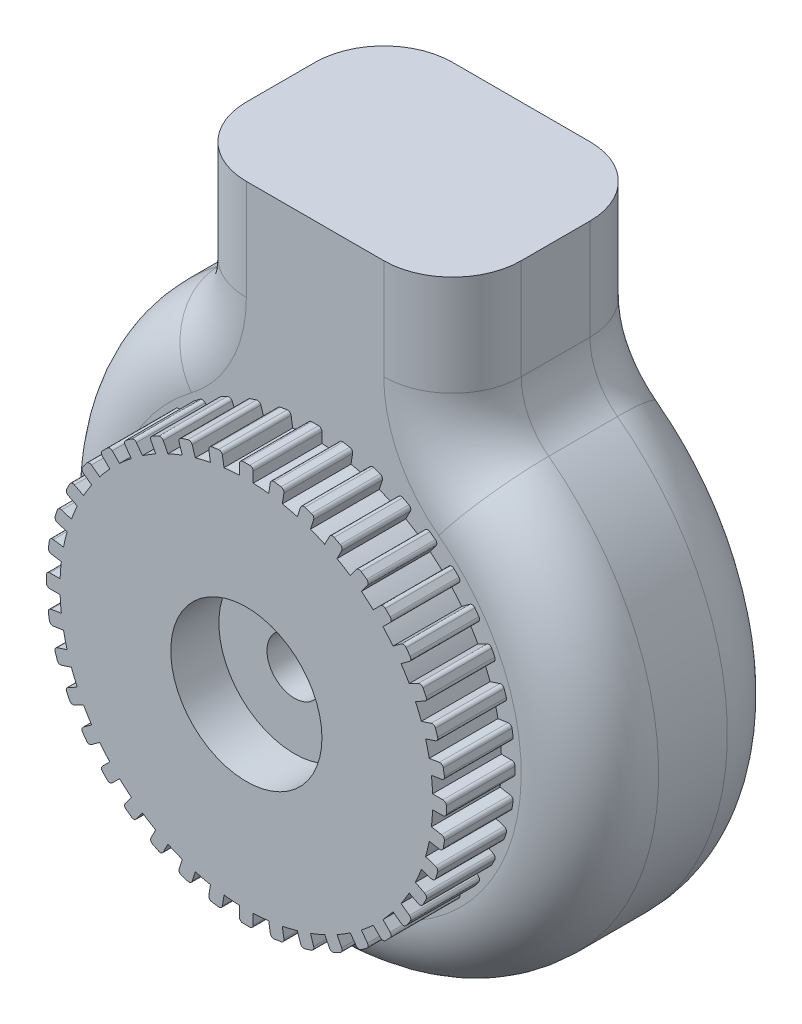
SolidWorks part; units mm, degrees
material "ABS"
ref_plane "Plan de face" through (0, 0, 0) normal (0, 0, 1) x (1, 0, 0)
ref_plane "Plan de dessus" through (0, 0, 0) normal (0, 1, 0) x (1, 0, 0)
ref_plane "Plan de droite" through (0, 0, 0) normal (1, 0, 0) x (0, 0, -1)
sketch "Esquisse1" plane through (0, 0, 0) normal (0, 0, 1) x (1, 0, 0)
  line L0 (0, -1000) -> (0, 49000) construction
  line L1 (-20, 34.641) -> (-20, 54.641)
  line L2 (-20, 54.641) -> (20, 54.641)
  line L3 (20, 34.641) -> (20, 54.641)
  circle A0 centre (0, 0) radius 40
  point P3 (-20, 34.641)
  point P11 (0, 54.641)
  dimension "D1" = 80
  dimension "D2" = 20
  dimension "D3" = 20
extrude "Boss.-Extru.1" add sketch "Esquisse1" along normal blind 15 and the other way blind 15 contours A0 L0 | A0 L0 L2 L1 | L0 A0 L3 L2 | L0 A0 region at (-16.9765, 0, 0) region at (16.9765, 0, 0) region at (-10.5372, 46.3765, 0) region at (10.5372, 46.3765, 0)
sketch "Esquisse3" plane through (0, 0, -15) normal (0, 0, -1) x (-1, 0, 0)
  circle A0 centre (0, 0) radius 15
  dimension "D1" = 30
extrude "Boss.-Extru.2" add sketch "Esquisse3" along normal blind 10
sketch "Esquisse4" plane through (0, 0, 15) normal (0, 0, 1) x (1, 0, 0)
  line L0 (0, -1000) -> (0, 49000) construction
  line L1 (-1, 27.1005) -> (-1, 28.6005)
  line L2 (-0.5, 29.1005) -> (0.5, 29.1005)
  line L3 (1, 27.1005) -> (1, 28.6005)
  line L4 (5.2271, 26.6104) -> (5.4618, 28.0919)
  line L5 (3.2518, 26.9232) -> (3.4864, 28.4048)
  line L6 (4.0585, 28.8204) -> (5.0462, 28.664)
  line L7 (9.3256, 25.465) -> (9.7891, 26.8916)
  line L8 (7.4234, 26.0831) -> (7.887, 27.5097)
  line L9 (8.517, 27.8307) -> (9.4681, 27.5217)
  line L10 (13.1944, 23.6927) -> (13.8753, 25.0292)
  line L11 (11.4123, 24.6007) -> (12.0933, 25.9372)
  line L12 (12.7658, 26.1557) -> (13.6568, 25.7017)
  line L13 (16.7383, 21.3369) -> (17.6199, 22.5505)
  line L14 (15.1202, 22.5125) -> (16.0019, 23.726)
  line L15 (16.7003, 23.8367) -> (17.5093, 23.2489)
  line L16 (19.87, 18.4558) -> (20.9307, 19.5165)
  line L17 (18.4558, 19.87) -> (19.5165, 20.9307)
  line L18 (20.2236, 20.9307) -> (20.9307, 20.2236)
  line L19 (22.5125, 15.1202) -> (23.726, 16.0019)
  line L20 (21.3369, 16.7383) -> (22.5505, 17.6199)
  line L21 (23.2489, 17.5093) -> (23.8367, 16.7003)
  line L22 (24.6007, 11.4123) -> (25.9372, 12.0933)
  line L23 (23.6927, 13.1944) -> (25.0292, 13.8753)
  line L24 (25.7017, 13.6568) -> (26.1557, 12.7658)
  line L25 (26.0831, 7.4234) -> (27.5097, 7.887)
  line L26 (25.465, 9.3256) -> (26.8916, 9.7891)
  line L27 (27.5217, 9.4681) -> (27.8307, 8.517)
  line L28 (26.9232, 3.2518) -> (28.4048, 3.4864)
  line L29 (26.6104, 5.2271) -> (28.0919, 5.4618)
  line L30 (28.664, 5.0462) -> (28.8204, 4.0585)
  line L31 (27.1005, -1) -> (28.6005, -1)
  line L32 (27.1005, 1) -> (28.6005, 1)
  line L33 (29.1005, 0.5) -> (29.1005, -0.5)
  line L34 (26.6104, -5.2271) -> (28.0919, -5.4618)
  line L35 (26.9232, -3.2518) -> (28.4048, -3.4864)
  line L36 (28.8204, -4.0585) -> (28.664, -5.0462)
  line L37 (25.465, -9.3256) -> (26.8916, -9.7891)
  line L38 (26.0831, -7.4234) -> (27.5097, -7.887)
  line L39 (27.8307, -8.517) -> (27.5217, -9.4681)
  line L40 (23.6927, -13.1944) -> (25.0292, -13.8753)
  line L41 (24.6007, -11.4123) -> (25.9372, -12.0933)
  line L42 (26.1557, -12.7658) -> (25.7017, -13.6568)
  line L43 (21.3369, -16.7383) -> (22.5505, -17.6199)
  line L44 (22.5125, -15.1202) -> (23.726, -16.0019)
  line L45 (23.8367, -16.7003) -> (23.2489, -17.5093)
  line L46 (18.4558, -19.87) -> (19.5165, -20.9307)
  line L47 (19.87, -18.4558) -> (20.9307, -19.5165)
  line L48 (20.9307, -20.2236) -> (20.2236, -20.9307)
  line L49 (15.1202, -22.5125) -> (16.0019, -23.726)
  line L50 (16.7383, -21.3369) -> (17.6199, -22.5505)
  line L51 (17.5093, -23.2489) -> (16.7003, -23.8367)
  line L52 (11.4123, -24.6007) -> (12.0933, -25.9372)
  line L53 (13.1944, -23.6927) -> (13.8753, -25.0292)
  line L54 (13.6568, -25.7017) -> (12.7658, -26.1557)
  line L55 (7.4234, -26.0831) -> (7.887, -27.5097)
  line L56 (9.3256, -25.465) -> (9.7891, -26.8916)
  line L57 (9.4681, -27.5217) -> (8.517, -27.8307)
  line L58 (3.2518, -26.9232) -> (3.4864, -28.4048)
  line L59 (5.2271, -26.6104) -> (5.4618, -28.0919)
  line L60 (5.0462, -28.664) -> (4.0585, -28.8204)
  line L61 (-1, -27.1005) -> (-1, -28.6005)
  line L62 (1, -27.1005) -> (1, -28.6005)
  line L63 (0.5, -29.1005) -> (-0.5, -29.1005)
  line L64 (-5.2271, -26.6104) -> (-5.4618, -28.0919)
  line L65 (-3.2518, -26.9232) -> (-3.4864, -28.4048)
  line L66 (-4.0585, -28.8204) -> (-5.0462, -28.664)
  line L67 (-9.3256, -25.465) -> (-9.7891, -26.8916)
  line L68 (-7.4234, -26.0831) -> (-7.887, -27.5097)
  line L69 (-8.517, -27.8307) -> (-9.4681, -27.5217)
  line L70 (-13.1944, -23.6927) -> (-13.8753, -25.0292)
  line L71 (-11.4123, -24.6007) -> (-12.0933, -25.9372)
  line L72 (-12.7658, -26.1557) -> (-13.6568, -25.7017)
  line L73 (-16.7383, -21.3369) -> (-17.6199, -22.5505)
  line L74 (-15.1202, -22.5125) -> (-16.0019, -23.726)
  line L75 (-16.7003, -23.8367) -> (-17.5093, -23.2489)
  line L76 (-19.87, -18.4558) -> (-20.9307, -19.5165)
  line L77 (-18.4558, -19.87) -> (-19.5165, -20.9307)
  line L78 (-20.2236, -20.9307) -> (-20.9307, -20.2236)
  line L79 (-22.5125, -15.1202) -> (-23.726, -16.0019)
  line L80 (-21.3369, -16.7383) -> (-22.5505, -17.6199)
  line L81 (-23.2489, -17.5093) -> (-23.8367, -16.7003)
  line L82 (-24.6007, -11.4123) -> (-25.9372, -12.0933)
  line L83 (-23.6927, -13.1944) -> (-25.0292, -13.8753)
  line L84 (-25.7017, -13.6568) -> (-26.1557, -12.7658)
  line L85 (-26.0831, -7.4234) -> (-27.5097, -7.887)
  line L86 (-25.465, -9.3256) -> (-26.8916, -9.7891)
  line L87 (-27.5217, -9.4681) -> (-27.8307, -8.517)
  line L88 (-26.9232, -3.2518) -> (-28.4048, -3.4864)
  line L89 (-26.6104, -5.2271) -> (-28.0919, -5.4618)
  line L90 (-28.664, -5.0462) -> (-28.8204, -4.0585)
  line L91 (-27.1005, 1) -> (-28.6005, 1)
  line L92 (-27.1005, -1) -> (-28.6005, -1)
  line L93 (-29.1005, -0.5) -> (-29.1005, 0.5)
  line L94 (-26.6104, 5.2271) -> (-28.0919, 5.4618)
  line L95 (-26.9232, 3.2518) -> (-28.4048, 3.4864)
  line L96 (-28.8204, 4.0585) -> (-28.664, 5.0462)
  line L97 (-25.465, 9.3256) -> (-26.8916, 9.7891)
  line L98 (-26.0831, 7.4234) -> (-27.5097, 7.887)
  line L99 (-27.8307, 8.517) -> (-27.5217, 9.4681)
  line L100 (-23.6927, 13.1944) -> (-25.0292, 13.8753)
  line L101 (-24.6007, 11.4123) -> (-25.9372, 12.0933)
  line L102 (-26.1557, 12.7658) -> (-25.7017, 13.6568)
  line L103 (-21.3369, 16.7383) -> (-22.5505, 17.6199)
  line L104 (-22.5125, 15.1202) -> (-23.726, 16.0019)
  line L105 (-23.8367, 16.7003) -> (-23.2489, 17.5093)
  line L106 (-18.4558, 19.87) -> (-19.5165, 20.9307)
  line L107 (-19.87, 18.4558) -> (-20.9307, 19.5165)
  line L108 (-20.9307, 20.2236) -> (-20.2236, 20.9307)
  line L109 (-15.1202, 22.5125) -> (-16.0019, 23.726)
  line L110 (-16.7383, 21.3369) -> (-17.6199, 22.5505)
  line L111 (-17.5093, 23.2489) -> (-16.7003, 23.8367)
  line L112 (-11.4123, 24.6007) -> (-12.0933, 25.9372)
  line L113 (-13.1944, 23.6927) -> (-13.8753, 25.0292)
  line L114 (-13.6568, 25.7017) -> (-12.7658, 26.1557)
  line L115 (-7.4234, 26.0831) -> (-7.887, 27.5097)
  line L116 (-9.3256, 25.465) -> (-9.7891, 26.8916)
  line L117 (-9.4681, 27.5217) -> (-8.517, 27.8307)
  line L118 (-3.2518, 26.9232) -> (-3.4864, 28.4048)
  line L119 (-5.2271, 26.6104) -> (-5.4618, 28.0919)
  line L120 (-5.0462, 28.664) -> (-4.0585, 28.8204)
  arc A1 (-1, 28.6005) -> (-0.5, 29.1005) centre (-0.5, 28.6005) cw
  arc A2 (1, 28.6005) -> (0.5, 29.1005) centre (0.5, 28.6005) ccw
  arc A3 (5.4618, 28.0919) -> (5.0462, 28.664) centre (4.9679, 28.1701) ccw
  arc A4 (3.4864, 28.4048) -> (4.0585, 28.8204) centre (3.9803, 28.3266) cw
  arc A5 (9.7891, 26.8916) -> (9.4681, 27.5217) centre (9.3136, 27.0461) ccw
  arc A6 (7.887, 27.5097) -> (8.517, 27.8307) centre (8.3625, 27.3552) cw
  arc A7 (13.8753, 25.0292) -> (13.6568, 25.7017) centre (13.4298, 25.2562) ccw
  arc A8 (12.0933, 25.9372) -> (12.7658, 26.1557) centre (12.5388, 25.7102) cw
  arc A9 (17.6199, 22.5505) -> (17.5093, 23.2489) centre (17.2154, 22.8444) ccw
  arc A10 (16.0019, 23.726) -> (16.7003, 23.8367) centre (16.4064, 23.4321) cw
  arc A11 (20.9307, 19.5165) -> (20.9307, 20.2236) centre (20.5771, 19.87) ccw
  arc A12 (19.5165, 20.9307) -> (20.2236, 20.9307) centre (19.87, 20.5771) cw
  arc A13 (23.726, 16.0019) -> (23.8367, 16.7003) centre (23.4321, 16.4064) ccw
  arc A14 (22.5505, 17.6199) -> (23.2489, 17.5093) centre (22.8444, 17.2154) cw
  arc A15 (25.9372, 12.0933) -> (26.1557, 12.7658) centre (25.7102, 12.5388) ccw
  arc A16 (25.0292, 13.8753) -> (25.7017, 13.6568) centre (25.2562, 13.4298) cw
  arc A17 (27.5097, 7.887) -> (27.8307, 8.517) centre (27.3552, 8.3625) ccw
  arc A18 (26.8916, 9.7891) -> (27.5217, 9.4681) centre (27.0461, 9.3136) cw
  arc A19 (28.4048, 3.4864) -> (28.8204, 4.0585) centre (28.3266, 3.9803) ccw
  arc A20 (28.0919, 5.4618) -> (28.664, 5.0462) centre (28.1701, 4.9679) cw
  arc A21 (28.6005, -1) -> (29.1005, -0.5) centre (28.6005, -0.5) ccw
  arc A22 (28.6005, 1) -> (29.1005, 0.5) centre (28.6005, 0.5) cw
  arc A23 (28.0919, -5.4618) -> (28.664, -5.0462) centre (28.1701, -4.9679) ccw
  arc A24 (28.4048, -3.4864) -> (28.8204, -4.0585) centre (28.3266, -3.9803) cw
  arc A25 (26.8916, -9.7891) -> (27.5217, -9.4681) centre (27.0461, -9.3136) ccw
  arc A26 (27.5097, -7.887) -> (27.8307, -8.517) centre (27.3552, -8.3625) cw
  arc A27 (25.0292, -13.8753) -> (25.7017, -13.6568) centre (25.2562, -13.4298) ccw
  arc A28 (25.9372, -12.0933) -> (26.1557, -12.7658) centre (25.7102, -12.5388) cw
  arc A29 (22.5505, -17.6199) -> (23.2489, -17.5093) centre (22.8444, -17.2154) ccw
  arc A30 (23.726, -16.0019) -> (23.8367, -16.7003) centre (23.4321, -16.4064) cw
  arc A31 (19.5165, -20.9307) -> (20.2236, -20.9307) centre (19.87, -20.5771) ccw
  arc A32 (20.9307, -19.5165) -> (20.9307, -20.2236) centre (20.5771, -19.87) cw
  arc A33 (16.0019, -23.726) -> (16.7003, -23.8367) centre (16.4064, -23.4321) ccw
  arc A34 (17.6199, -22.5505) -> (17.5093, -23.2489) centre (17.2154, -22.8444) cw
  arc A35 (12.0933, -25.9372) -> (12.7658, -26.1557) centre (12.5388, -25.7102) ccw
  arc A36 (13.8753, -25.0292) -> (13.6568, -25.7017) centre (13.4298, -25.2562) cw
  arc A37 (7.887, -27.5097) -> (8.517, -27.8307) centre (8.3625, -27.3552) ccw
  arc A38 (9.7891, -26.8916) -> (9.4681, -27.5217) centre (9.3136, -27.0461) cw
  arc A39 (3.4864, -28.4048) -> (4.0585, -28.8204) centre (3.9803, -28.3266) ccw
  arc A40 (5.4618, -28.0919) -> (5.0462, -28.664) centre (4.9679, -28.1701) cw
  arc A41 (-1, -28.6005) -> (-0.5, -29.1005) centre (-0.5, -28.6005) ccw
  arc A42 (1, -28.6005) -> (0.5, -29.1005) centre (0.5, -28.6005) cw
  arc A43 (-5.4618, -28.0919) -> (-5.0462, -28.664) centre (-4.9679, -28.1701) ccw
  arc A44 (-3.4864, -28.4048) -> (-4.0585, -28.8204) centre (-3.9803, -28.3266) cw
  arc A45 (-9.7891, -26.8916) -> (-9.4681, -27.5217) centre (-9.3136, -27.0461) ccw
  arc A46 (-7.887, -27.5097) -> (-8.517, -27.8307) centre (-8.3625, -27.3552) cw
  arc A47 (-13.8753, -25.0292) -> (-13.6568, -25.7017) centre (-13.4298, -25.2562) ccw
  arc A48 (-12.0933, -25.9372) -> (-12.7658, -26.1557) centre (-12.5388, -25.7102) cw
  arc A49 (-17.6199, -22.5505) -> (-17.5093, -23.2489) centre (-17.2154, -22.8444) ccw
  arc A50 (-16.0019, -23.726) -> (-16.7003, -23.8367) centre (-16.4064, -23.4321) cw
  arc A51 (-20.9307, -19.5165) -> (-20.9307, -20.2236) centre (-20.5771, -19.87) ccw
  arc A52 (-19.5165, -20.9307) -> (-20.2236, -20.9307) centre (-19.87, -20.5771) cw
  arc A53 (-23.726, -16.0019) -> (-23.8367, -16.7003) centre (-23.4321, -16.4064) ccw
  arc A54 (-22.5505, -17.6199) -> (-23.2489, -17.5093) centre (-22.8444, -17.2154) cw
  arc A55 (-25.9372, -12.0933) -> (-26.1557, -12.7658) centre (-25.7102, -12.5388) ccw
  arc A56 (-25.0292, -13.8753) -> (-25.7017, -13.6568) centre (-25.2562, -13.4298) cw
  arc A57 (-27.5097, -7.887) -> (-27.8307, -8.517) centre (-27.3552, -8.3625) ccw
  arc A58 (-26.8916, -9.7891) -> (-27.5217, -9.4681) centre (-27.0461, -9.3136) cw
  arc A59 (-28.4048, -3.4864) -> (-28.8204, -4.0585) centre (-28.3266, -3.9803) ccw
  arc A60 (-28.0919, -5.4618) -> (-28.664, -5.0462) centre (-28.1701, -4.9679) cw
  arc A61 (-28.6005, 1) -> (-29.1005, 0.5) centre (-28.6005, 0.5) ccw
  arc A62 (-28.6005, -1) -> (-29.1005, -0.5) centre (-28.6005, -0.5) cw
  arc A63 (-28.0919, 5.4618) -> (-28.664, 5.0462) centre (-28.1701, 4.9679) ccw
  arc A64 (-28.4048, 3.4864) -> (-28.8204, 4.0585) centre (-28.3266, 3.9803) cw
  arc A65 (-26.8916, 9.7891) -> (-27.5217, 9.4681) centre (-27.0461, 9.3136) ccw
  arc A66 (-27.5097, 7.887) -> (-27.8307, 8.517) centre (-27.3552, 8.3625) cw
  arc A67 (-25.0292, 13.8753) -> (-25.7017, 13.6568) centre (-25.2562, 13.4298) ccw
  arc A68 (-25.9372, 12.0933) -> (-26.1557, 12.7658) centre (-25.7102, 12.5388) cw
  arc A69 (-22.5505, 17.6199) -> (-23.2489, 17.5093) centre (-22.8444, 17.2154) ccw
  arc A70 (-23.726, 16.0019) -> (-23.8367, 16.7003) centre (-23.4321, 16.4064) cw
  arc A71 (-19.5165, 20.9307) -> (-20.2236, 20.9307) centre (-19.87, 20.5771) ccw
  arc A72 (-20.9307, 19.5165) -> (-20.9307, 20.2236) centre (-20.5771, 19.87) cw
  arc A73 (-16.0019, 23.726) -> (-16.7003, 23.8367) centre (-16.4064, 23.4321) ccw
  arc A74 (-17.6199, 22.5505) -> (-17.5093, 23.2489) centre (-17.2154, 22.8444) cw
  arc A75 (-12.0933, 25.9372) -> (-12.7658, 26.1557) centre (-12.5388, 25.7102) ccw
  arc A76 (-13.8753, 25.0292) -> (-13.6568, 25.7017) centre (-13.4298, 25.2562) cw
  arc A77 (-7.887, 27.5097) -> (-8.517, 27.8307) centre (-8.3625, 27.3552) ccw
  arc A78 (-9.7891, 26.8916) -> (-9.4681, 27.5217) centre (-9.3136, 27.0461) cw
  arc A79 (-3.4864, 28.4048) -> (-4.0585, 28.8204) centre (-3.9803, 28.3266) ccw
  arc A80 (-5.4618, 28.0919) -> (-5.0462, 28.664) centre (-4.9679, 28.1701) cw
  arc A81 (1, 27.1005) -> (3.2518, 26.9232) centre (0, 0) cw
  arc A82 (5.2271, 26.6104) -> (7.4234, 26.0831) centre (0, 0) cw
  arc A83 (9.3256, 25.465) -> (11.4123, 24.6007) centre (0, 0) cw
  arc A84 (13.1944, 23.6927) -> (15.1202, 22.5125) centre (0, 0) cw
  arc A85 (16.7383, 21.3369) -> (18.4558, 19.87) centre (0, 0) cw
  arc A86 (19.87, 18.4558) -> (21.3369, 16.7383) centre (0, 0) cw
  arc A87 (22.5125, 15.1202) -> (23.6927, 13.1944) centre (0, 0) cw
  arc A88 (24.6007, 11.4123) -> (25.465, 9.3256) centre (0, 0) cw
  arc A89 (26.0831, 7.4234) -> (26.6104, 5.2271) centre (0, 0) cw
  arc A90 (26.9232, 3.2518) -> (27.1005, 1) centre (0, 0) cw
  arc A91 (27.1005, -1) -> (26.9232, -3.2518) centre (0, 0) cw
  arc A92 (26.6104, -5.2271) -> (26.0831, -7.4234) centre (0, 0) cw
  arc A93 (25.465, -9.3256) -> (24.6007, -11.4123) centre (0, 0) cw
  arc A94 (23.6927, -13.1944) -> (22.5125, -15.1202) centre (0, 0) cw
  arc A95 (21.3369, -16.7383) -> (19.87, -18.4558) centre (0, 0) cw
  arc A96 (18.4558, -19.87) -> (16.7383, -21.3369) centre (0, 0) cw
  arc A97 (15.1202, -22.5125) -> (13.1944, -23.6927) centre (0, 0) cw
  arc A98 (11.4123, -24.6007) -> (9.3256, -25.465) centre (0, 0) cw
  arc A99 (7.4234, -26.0831) -> (5.2271, -26.6104) centre (0, 0) cw
  arc A100 (3.2518, -26.9232) -> (1, -27.1005) centre (0, 0) cw
  arc A101 (-1, -27.1005) -> (-3.2518, -26.9232) centre (0, 0) cw
  arc A102 (-5.2271, -26.6104) -> (-7.4234, -26.0831) centre (0, 0) cw
  arc A103 (-9.3256, -25.465) -> (-11.4123, -24.6007) centre (0, 0) cw
  arc A104 (-13.1944, -23.6927) -> (-15.1202, -22.5125) centre (0, 0) cw
  arc A105 (-16.7383, -21.3369) -> (-18.4558, -19.87) centre (0, 0) cw
  arc A106 (-19.87, -18.4558) -> (-21.3369, -16.7383) centre (0, 0) cw
  arc A107 (-22.5125, -15.1202) -> (-23.6927, -13.1944) centre (0, 0) cw
  arc A108 (-24.6007, -11.4123) -> (-25.465, -9.3256) centre (0, 0) cw
  arc A109 (-26.0831, -7.4234) -> (-26.6104, -5.2271) centre (0, 0) cw
  arc A110 (-26.9232, -3.2518) -> (-27.1005, -1) centre (0, 0) cw
  arc A111 (-27.1005, 1) -> (-26.9232, 3.2518) centre (0, 0) cw
  arc A112 (-26.6104, 5.2271) -> (-26.0831, 7.4234) centre (0, 0) cw
  arc A113 (-25.465, 9.3256) -> (-24.6007, 11.4123) centre (0, 0) cw
  arc A114 (-23.6927, 13.1944) -> (-22.5125, 15.1202) centre (0, 0) cw
  arc A115 (-21.3369, 16.7383) -> (-19.87, 18.4558) centre (0, 0) cw
  arc A116 (-18.4558, 19.87) -> (-16.7383, 21.3369) centre (0, 0) cw
  arc A117 (-15.1202, 22.5125) -> (-13.1944, 23.6927) centre (0, 0) cw
  arc A118 (-11.4123, 24.6007) -> (-9.3256, 25.465) centre (0, 0) cw
  arc A119 (-7.4234, 26.0831) -> (-5.2271, 26.6104) centre (0, 0) cw
  arc A120 (-3.2518, 26.9232) -> (-1, 27.1005) centre (0, 0) cw
  point P3 (-1, 27.1005)
  point P11 (-1, 29.1005)
  point P13 (0, 29.1005)
  point P329 (0, 0)
  point P409 (0, 0)
  dimension "D3" = 0.5
  dimension "D1" = 1
  dimension "D2" = 2
  dimension "D4" = 40
  dimension "D5" = 40
extrude "Boss.-Extru.3" add sketch "Esquisse4" along normal blind 10
sketch "Esquisse5" plane through (0, 0, 25) normal (0, 0, 1) x (1, 0, 0)
  circle A0 centre (0, 0) radius 4
  dimension "D1" = 8
extrude "Enlèv. mat.-Extru.1" cut sketch "Esquisse5" against normal up to next
sketch "Esquisse6" plane through (0, 0, 25) normal (0, 0, 1) x (1, 0, 0)
  circle A0 centre (0, 0) radius 11
  dimension "D1" = 22
extrude "Enlèv. mat.-Extru.2" cut sketch "Esquisse6" against normal blind 7
sketch "Esquisse7" plane through (0, 0, -25) normal (0, 0, -1) x (-1, 0, 0)
  circle A0 centre (0, 0) radius 11
  dimension "D1" = 22
extrude "Enlèv. mat.-Extru.3" cut sketch "Esquisse7" against normal blind 7
fillet "Congé2" radius 10 8 edges at (-20, 44.641, -15) (20, 44.641, -15) (-20, 44.641, 15) (20, 44.641, 15) (0, -40, -15) (-20, 34.641, 0) (0, -40, 15) (20, 34.641, 0)
